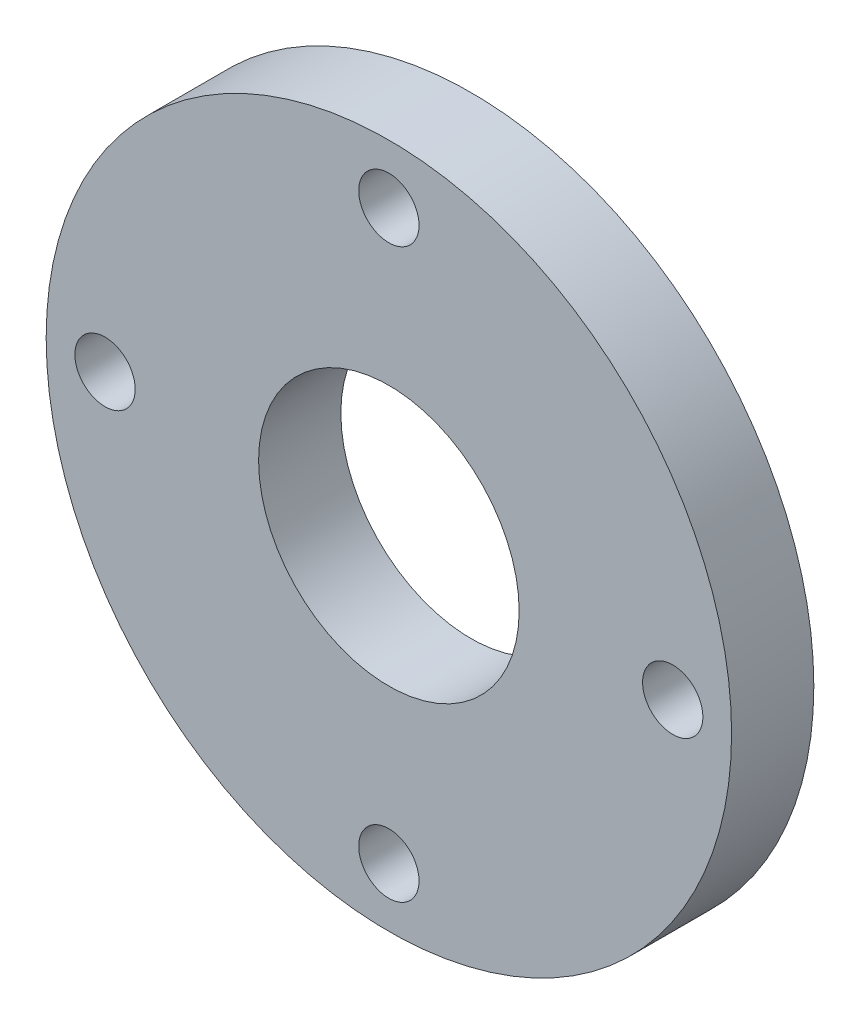
SolidWorks part; units mm, degrees
ref_plane "Front Plane" through (0, 0, 0) normal (0, 0, 1) x (1, 0, 0)
ref_plane "Top Plane" through (0, 0, 0) normal (0, 1, 0) x (1, 0, 0)
ref_plane "Right Plane" through (0, 0, 0) normal (1, 0, 0) x (0, 0, -1)
sketch "Sketch1" plane through (0, 0, 0) normal (1, 0, 0) x (0, 0, -1)
  line L0 (-108, -9.5) -> (-149, -9.5)
  line L5 (-1000, 0) -> (49000, 0)
  line L6 (0, -9.5) -> (0, 9.5)
  line L13 (0, 9.5) -> (-46.4, 9.5)
  line L26 (-46.4, 9.5) -> (-46.4, 14)
  line L27 (-46.4, 14) -> (-108, 14)
  line L32 (-108, 14) -> (-108, 9.5)
  line L34 (-165, 7) -> (-165, -7)
  line L36 (-108, -9.5) -> (-108, -14)
  line L37 (-108, -14) -> (-46.4, -14)
  line L38 (-46.4, -14) -> (-46.4, -9.5)
  line L39 (0, -9.5) -> (-46.4, -9.5)
  line L40 (-22.625, 37.5) -> (-13.625, 37.5)
  line L41 (-124.6, 22.6187) -> (-108, 22.6187)
  line L42 (-124.6, 22.6187) -> (-124.6, -22.6187)
  line L43 (-124.6, -22.6187) -> (-108, -22.6187)
  line L44 (-108, 22.6187) -> (-108, -22.6187)
  line L45 (-124.6, 22.6187) -> (-108, -22.6187) construction
  line L46 (-124.6, -22.6187) -> (-108, 22.6187) construction
  line L47 (-29.8, 22.6187) -> (-46.4, 22.6187)
  line L48 (-29.8, 22.6187) -> (-29.8, -22.6187)
  line L49 (-29.8, -22.6187) -> (-46.4, -22.6187)
  line L50 (-46.4, 22.6187) -> (-46.4, -22.6187)
  line L51 (-29.8, 22.6187) -> (-46.4, -22.6187) construction
  line L52 (-29.8, -22.6187) -> (-46.4, 22.6187) construction
  line L59 (-13.625, 37.5) -> (-13.625, -37.5)
  line L60 (-13.625, -37.5) -> (-22.625, -37.5)
  line L61 (-22.625, -22.6187) -> (-26.625, -22.6187)
  line L62 (-26.625, -22.6187) -> (-26.625, -12.5)
  line L63 (-26.625, -12.5) -> (-22.625, -12.5)
  line L64 (-22.625, -12.5) -> (-22.625, 12.5)
  line L65 (-22.625, 12.5) -> (-26.625, 12.5)
  line L66 (-26.625, 12.5) -> (-26.625, 22.6187)
  line L67 (-26.625, 22.6187) -> (-22.625, 22.6187)
  line L68 (-22.625, 22.6187) -> (-22.625, 37.5)
  line L69 (-22.625, -22.6187) -> (-22.625, -37.5)
  line L71 (-136.284, 37.5) -> (-23.625, 37.5)
  line L72 (-136.284, 37.5) -> (-136.284, -37.5)
  line L73 (-136.284, -37.5) -> (-23.625, -37.5)
  line L74 (-23.625, 37.5) -> (-23.625, -37.5)
  line L75 (-136.284, 37.5) -> (-23.625, -37.5) construction
  line L76 (-136.284, -37.5) -> (-23.625, 37.5) construction
  line L77 (-149, -9.5) -> (-149, -7)
  line L78 (-149, -7) -> (-165, -7)
  line L79 (-108, 9.5) -> (-149, 9.5)
  line L80 (-149, 7) -> (-165, 7)
  line L81 (-149, 9.5) -> (-149, 7)
  line L82 (-128.5, 9.5) -> (-128.5, -9.5) construction
  line L83 (-23.2, 9.5) -> (-23.2, -9.5) construction
  line L96 (-136.284, 37.5) -> (-145.284, 37.5)
  line L98 (-136.284, -37.5) -> (-145.284, -37.5)
  line L99 (-145.284, 37.5) -> (-145.284, -37.5)
  line L110 (-136.284, 37.5) -> (-136.284, -37.5)
  point P3 (0, 0)
  point P18 (-116.3, 0)
  point P24 (-38.1, 0)
  point P29 (-79.9545, 0)
  point P48 (-13.625, 31.0593)
  point P70 (-145.284, 31.0593)
revolve "Main_body" add sketch "Sketch1" angle 360 about L5 region at (0, 23.5, 140.784)
sketch "Sketch5" plane through (0, 0, 145.284) normal (0, 0, 1) x (1, 0, 0)
  circle A0 centre (0, 0) radius 14.2558
  dimension "D1" = 28.5115
extrude "seal_seat" cut sketch "Sketch5" against normal through all
hole_wizard "M6 Clearance Hole1" positions "Sketch3" profile "Sketch4" hole size "M6" standard "ANSI Metric" end condition through all
sketch "Sketch3" plane through (0, 0, 145.284) normal (0, 0, 1) x (1, 0, 0)
  point P0 (0, 31.0593)
sketch "Sketch4" plane through (0, 31.0593, 145.284) normal (1, 0, 0) x (0, -1, 0)
  line L0 (0, 0) -> (0, 9)
  line L1 (0, 9) -> (3.3, 9)
  line L2 (3.3, 9) -> (3.3, 0)
  line L5 (3.3, 0) -> (0, 0)
  line L11 (0, -6.35) -> (0, 107.95) construction
  dimension "Thru Hole Dia." = 6.6
  dimension "Thru Hole Depth" = 9
pattern_circular "CirPattern1" count 4 over 360 about axis through (0, 0, 1000) along (0, 0, -1) of "M6 Clearance Hole1"
